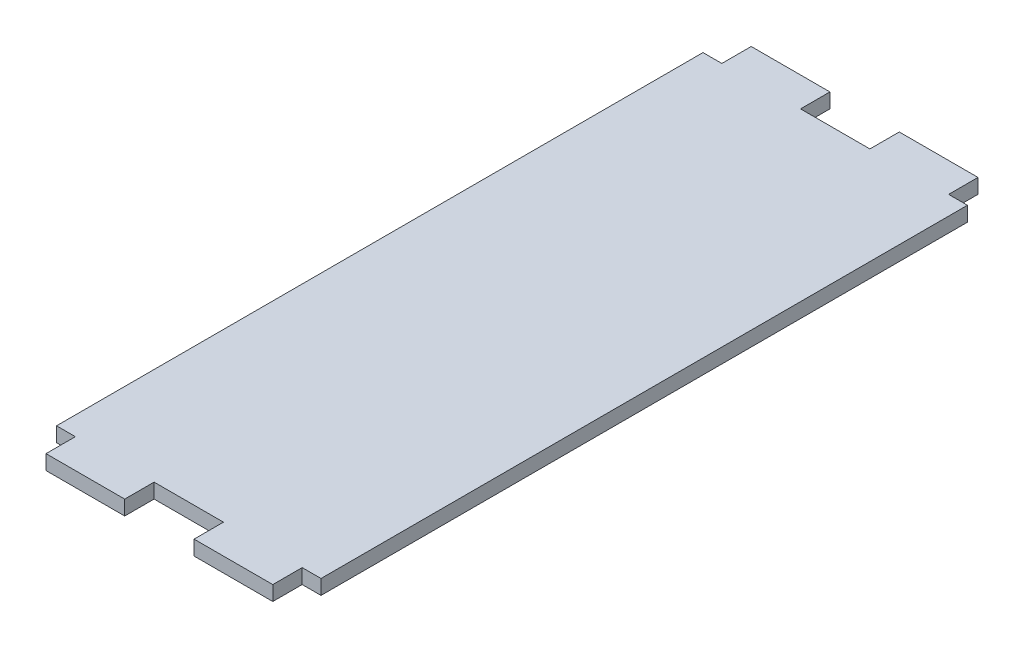
SolidWorks part; units mm, degrees
material "Cedar"
ref_plane "Front Plane" through (0, 0, 0) normal (0, 0, 1) x (1, 0, 0)
ref_plane "Top Plane" through (0, 0, 0) normal (0, 1, 0) x (1, 0, 0)
ref_plane "Right Plane" through (0, 0, 0) normal (1, 0, 0) x (0, 0, -1)
sketch "Sketch1" plane through (0, 0, 0) normal (0, 1, 0) x (1, 0, 0)
  line L1 (-28.575, 76.2) -> (28.575, 76.2)
  line L2 (-28.575, 76.2) -> (-28.575, -76.2)
  line L3 (-28.575, -76.2) -> (28.575, -76.2)
  line L4 (28.575, 76.2) -> (28.575, -76.2)
  line L5 (-28.575, 76.2) -> (28.575, -76.2) construction
  line L6 (-28.575, -76.2) -> (28.575, 76.2) construction
  point P0 (0, 0)
  dimension "D1" = 57.15
  dimension "D2" = 152.4
extrude "Boss-Extrude1" add sketch "Sketch1" along normal blind 3.175
sketch "Sketch2" plane through (0, 3.175, 0) normal (0, 1, 0) x (1, 0, 0)
  line L0 (-28.575, -69.85) -> (28.575, -69.85) construction
  line L1 (-28.575, 76.2) -> (-28.575, -76.2) construction
  line L2 (28.575, -76.2) -> (28.575, 76.2) construction
  line L3 (0, -76.2) -> (0, -69.85) construction
  line L4 (-28.575, -76.2) -> (28.575, -76.2) construction
  line L5 (-24.505, -69.85) -> (-28.575, -69.85)
  line L6 (-24.505, -69.85) -> (-7.495, -69.85) construction
  line L7 (-24.505, -69.85) -> (-24.505, -76.2)
  line L8 (-24.505, -76.2) -> (-7.495, -76.2) construction
  line L9 (-7.495, -69.85) -> (-7.495, -76.2)
  line L10 (-24.505, -69.85) -> (-7.495, -76.2) construction
  line L11 (-24.505, -76.2) -> (-7.495, -69.85) construction
  line L12 (-28.575, -69.85) -> (-28.575, -76.2)
  line L13 (-28.575, -76.2) -> (-24.505, -76.2)
  line L14 (-7.495, -76.2) -> (7.495, -76.2)
  line L15 (0, -76.2) -> (0, -69.85)
  line L16 (7.495, -69.85) -> (-7.495, -69.85)
  line L17 (24.505, -76.2) -> (7.495, -69.85) construction
  line L18 (24.505, -69.85) -> (7.495, -76.2) construction
  line L19 (24.505, -76.2) -> (7.495, -76.2) construction
  line L20 (24.505, -69.85) -> (7.495, -69.85) construction
  line L21 (28.575, -76.2) -> (24.505, -76.2)
  line L22 (28.575, -69.85) -> (28.575, -76.2)
  line L23 (7.495, -69.85) -> (7.495, -76.2)
  line L24 (24.505, -69.85) -> (24.505, -76.2)
  line L25 (24.505, -69.85) -> (28.575, -69.85)
  point P10 (-16, -73.025)
  point P22 (16, -73.025)
  line M12 (28.575, -76.2) -> (28.575, 76.2)
  line M14 (-28.575, 76.2) -> (-28.575, -76.2)
  line M15 (-28.575, -76.2) -> (28.575, -76.2)
  dimension "D1" = 6.35
  dimension "D2" = 7.495
  dimension "D3" = 17.01
extrude "Cut-Extrude1" cut sketch "Sketch2" against normal through all contours L7 L5 M14 M15 | L15 L16 L9 M15 | L23 L16 L15 L14 | L25 L24 M15 M12 region at (-26.54, 3.175, 73.025) region at (26.54, 3.175, 73.025) region at (-3.7475, 3.175, 73.025) region at (3.7475, 3.175, 73.025)
mirror "Mirror1" about plane through (0, 0, 0) normal (0, 0, 1) of "Cut-Extrude1"
